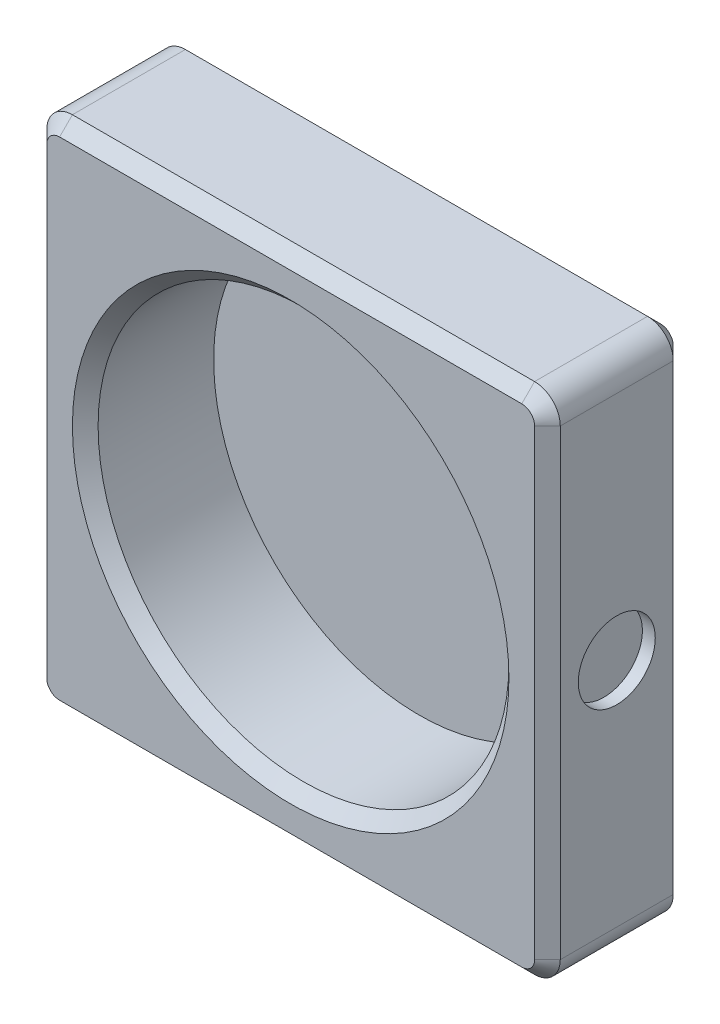
SolidWorks part; units mm, degrees
ref_plane "Front Plane" through (0, 0, 0) normal (0, 0, 1) x (1, 0, 0)
ref_plane "Top Plane" through (0, 0, 0) normal (0, 1, 0) x (1, 0, 0)
ref_plane "Right Plane" through (0, 0, 0) normal (1, 0, 0) x (0, 0, -1)
sketch "Sketch1" plane through (0, 0, 0) normal (0, 0, 1) x (1, 0, 0)
  line L1 (-10, -10) -> (10, -10)
  line L2 (-10, -10) -> (-10, 10)
  line L3 (-10, 10) -> (10, 10)
  line L4 (10, -10) -> (10, 10)
  line L5 (-10, -10) -> (10, 10) construction
  line L6 (-10, 10) -> (10, -10) construction
  point P0 (0, 0)
  dimension "D1" = 20
  dimension "D2" = 20
extrude "Boss-Extrude1" add sketch "Sketch1" along normal blind 5.4
sketch "Sketch2" plane through (0, 0, 5.4) normal (0, 0, 1) x (1, 0, 0)
  circle A0 centre (0, 0) radius 8
  dimension "D1" = 16
extrude "Cut-Extrude1" cut sketch "Sketch2" against normal blind 5
sketch "Sketch3" plane through (10, 0, 0) normal (1, 0, 0) x (0, 0, -1)
  line L0 (0, 0) -> (-5.4, 0) construction
  line L1 (-5.4, -10) -> (-5.4, 10) construction
  circle A0 centre (-2.7, 0) radius 1.5
  dimension "D1" = 3
extrude "Cut-Extrude2" cut sketch "Sketch3" against normal blind 0.5
fillet "Fillet1" radius 1 4 edges at (10, -10, 2.7) (-10, -10, 2.7) (-10, 10, 2.7) (10, 10, 2.7)
chamfer "Chamfer1" distance 0.5 angle 45 17 edges at (9.7071, 9.7071, 0) (0, 10, 0) (-9.7071, 9.7071, 0) (-10, 0, 0) (-9.7071, -9.7071, 0) (0, -10, 0) (9.7071, -9.7071, 0) (10, 0, 0) (-9.7071, -9.7071, 5.4) (-10, 0, 5.4) (-9.7071, 9.7071, 5.4) (0, 10, 5.4) (9.7071, 9.7071, 5.4) (10, 0, 5.4) (9.7071, -9.7071, 5.4) (0, -10, 5.4) (8, 0, 5.4)
